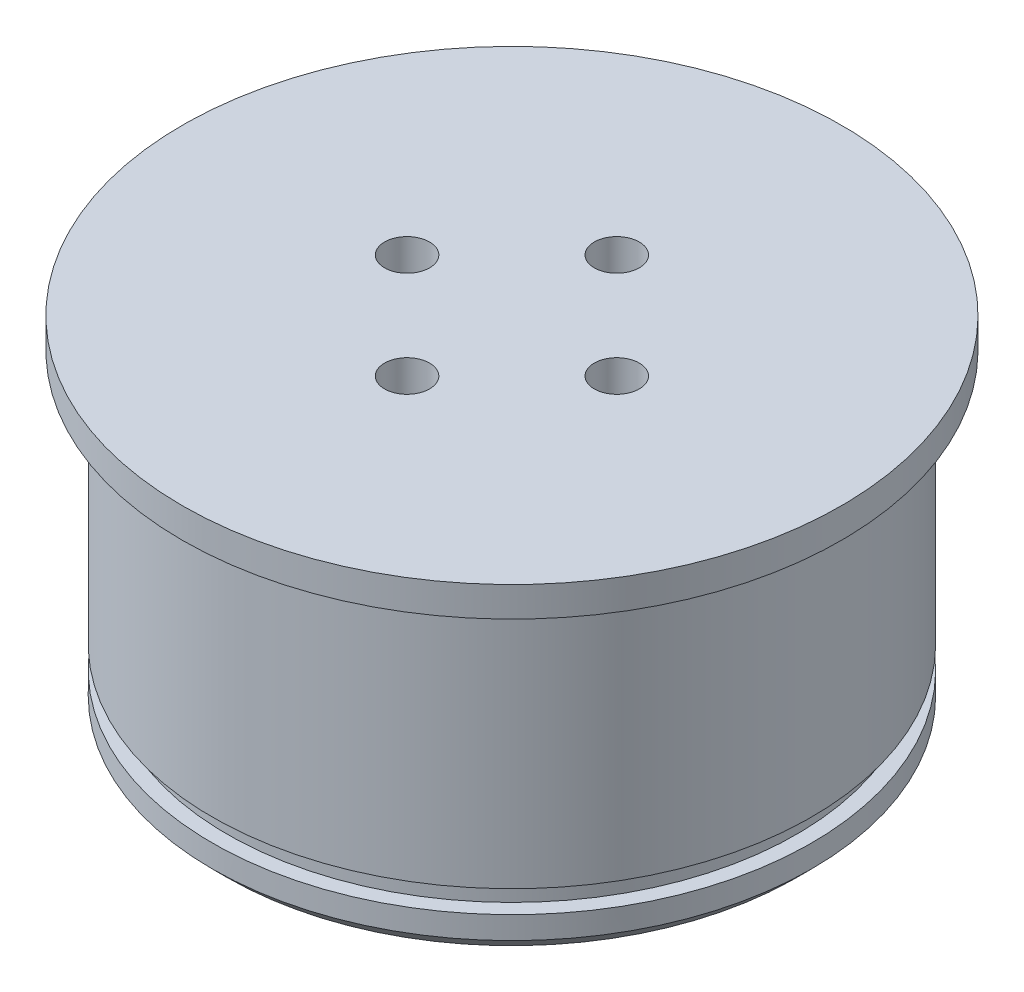
SolidWorks part; units mm, degrees
ref_plane "Спереди" through (0, 0, 0) normal (0, 0, 1) x (1, 0, 0)
ref_plane "Сверху" through (0, 0, 0) normal (0, 1, 0) x (1, 0, 0)
ref_plane "Справа" through (0, 0, 0) normal (1, 0, 0) x (0, 0, -1)
sketch "Эскиз1" plane through (0, 0, 0) normal (0, 1, 0) x (1, 0, 0)
  circle A0 centre (0, 0) radius 20
  dimension "D1" = 40
extrude "Бобышка-Вытянуть1" add sketch "Эскиз1" along normal blind 21
sketch "Эскиз2" plane through (0, 0, 0) normal (0, -1, 0) x (1, 0, 0)
  circle A0 centre (0, 0) radius 10
  dimension "D1" = 20
extrude "Вырез-Вытянуть2" cut sketch "Эскиз2" against normal blind 2.5
ref_plane "Плоскость1" through (0, 2.5, 0) normal (0, -1, 0) x (-1, 0, 0)
sketch "Эскиз5" plane through (0, 2.5, 0) normal (0, -1, 0) x (-1, 0, 0)
  circle A0 centre (0, 0) radius 19
  circle A1 centre (0, 0) radius 20
  dimension "D1" = 38
  dimension "D2" = 40
extrude "Вырез-Вытянуть5" cut sketch "Эскиз5" against normal blind 1.5
chamfer "Фаска1" distance 1 angle 45 1 edges at (0, 0, 20)
sketch "Эскиз6" plane through (0, 21, 0) normal (0, 1, 0) x (1, 0, 0)
  circle A0 centre (0, 0) radius 22
  dimension "D1" = 44
extrude "Бобышка-Вытянуть2" add sketch "Эскиз6" along normal blind 2
sketch "Эскиз4" plane through (0, 2.5, 0) normal (0, -1, 0) x (1, 0, 0)
  circle A0 centre (0, 7) radius 1.5
  dimension "D2" = 3
  dimension "D1" = 7
extrude "Вырез-Вытянуть6" cut sketch "Эскиз4" against normal through all
pattern_circular "Круговой массив1" count 4 over 360 about axis through (0, 2.5, 0) along (0, -1, 0) of "Вырез-Вытянуть6" reverse direction yes
